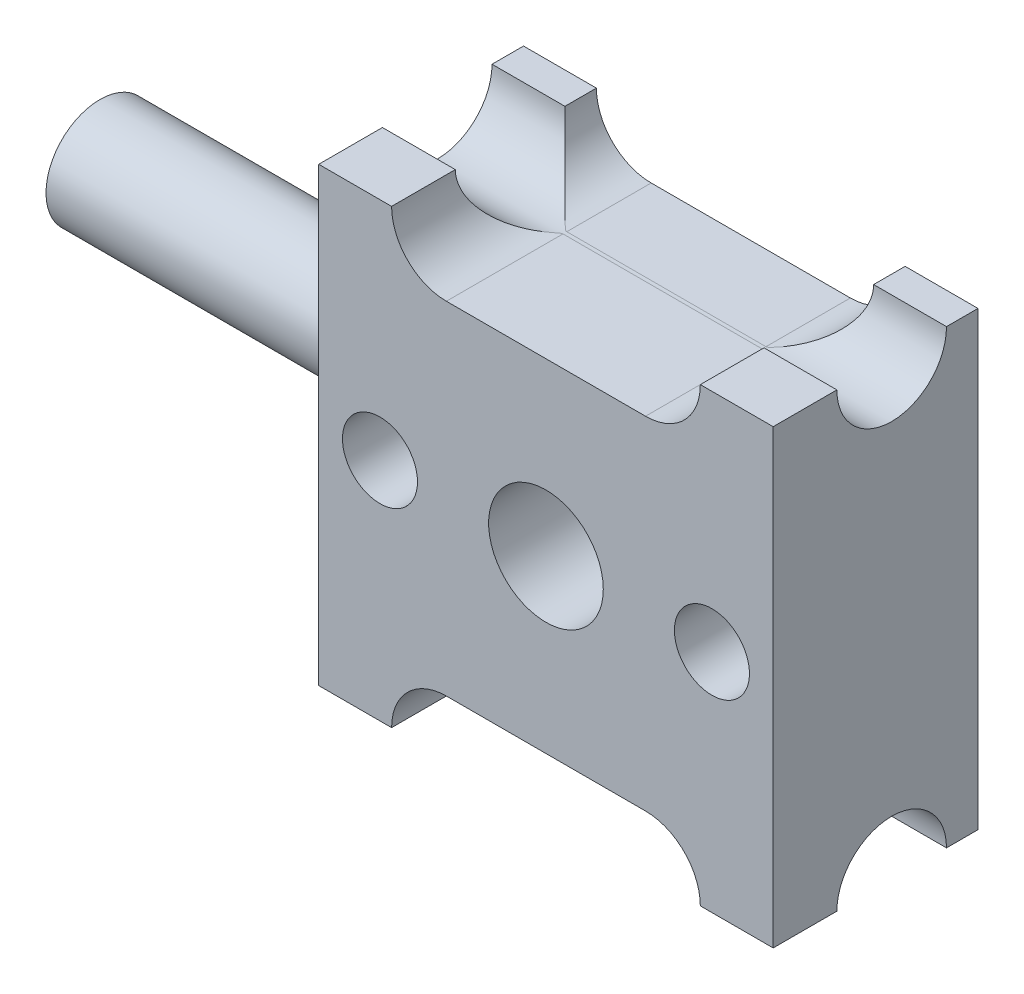
SolidWorks part; units mm, degrees
ref_plane "Front Plane" through (0, 0, 0) normal (0, 0, 1) x (1, 0, 0)
ref_plane "Top Plane" through (0, 0, 0) normal (0, 1, 0) x (1, 0, 0)
ref_plane "Right Plane" through (0, 0, 0) normal (1, 0, 0) x (0, 0, -1)
sketch "Sketch1" plane through (0, 0, 0) normal (0, 0, 1) x (1, 0, 0)
  line L1 (-6.8453, 6.8) -> (6.8453, 6.8)
  line L2 (-6.8453, 6.8) -> (-6.8453, -6.8)
  line L3 (-6.8453, -6.8) -> (6.8453, -6.8)
  line L4 (6.8453, 6.8) -> (6.8453, -6.8)
  line L5 (-6.8453, 6.8) -> (6.8453, -6.8) construction
  line L6 (-6.8453, -6.8) -> (6.8453, 6.8) construction
  point P0 (0, 0)
  dimension "D1" = 13.6906
  dimension "D2" = 13.6
extrude "Boss-Extrude1" add sketch "Sketch1" along normal blind 6.17
sketch "Sketch2" plane through (6.8453, 0, 0) normal (1, 0, 0) x (0, 0, -1)
  line L0 (-6.17, 6.8) -> (0, 6.8) construction
  line L1 (0, -6.8) -> (0, 6.8) construction
  line L2 (-6.17, 0) -> (0, 0) construction
  line L3 (-6.17, -6.8) -> (-6.17, 6.8) construction
  circle A0 centre (-2.6, 6.8) radius 1.651
  circle A1 centre (-2.6, -6.8) radius 1.651
  dimension "D2" = 3.302
  dimension "D1" = 2.6
extrude "Cut-Extrude1" cut sketch "Sketch2" against normal through all
sketch "Sketch3" plane through (0, 0, 6.17) normal (0, 0, 1) x (1, 0, 0)
  line L0 (6.8453, 6.8) -> (-6.8453, 6.8) construction
  line L1 (-3, 6.8) -> (3, 6.8)
  line L2 (-3, 6.8) -> (-3, 5.15)
  line L3 (-3, 5.15) -> (3, 5.15)
  line L4 (3, 6.8) -> (3, 5.15)
  line L5 (0, 5.15) -> (0, 7.1831) construction
  line L6 (-6.8453, 0) -> (0, 5.15) construction
  line L7 (-6.8453, 6.8) -> (-6.8453, -6.8) construction
  line L8 (0, 5.15) -> (6.8453, 0) construction
  line L9 (6.8453, -6.8) -> (6.8453, 6.8) construction
  line L10 (-6.8453, 0) -> (6.8453, 0) construction
  line L11 (0, -5.15) -> (6.8453, 0) construction
  line L12 (-6.8453, 0) -> (0, -5.15) construction
  line L13 (0, -5.15) -> (0, -7.1831) construction
  line L14 (3, -6.8) -> (3, -5.15)
  line L15 (-3, -5.15) -> (3, -5.15)
  line L16 (-3, -6.8) -> (-3, -5.15)
  line L17 (-3, -6.8) -> (3, -6.8)
  line L18 (-4.65, 6.8) -> (4.65, 6.8)
  line L19 (-3, -6.8) -> (3, -6.8)
  arc A0 (3, 5.15) -> (4.65, 6.8) centre (3, 6.8) ccw
  arc A1 (-3, 5.15) -> (-4.65, 6.8) centre (-3, 6.8) cw
  arc A2 (-3, -5.15) -> (-4.65, -6.8) centre (-3, -6.8) ccw
  arc A3 (3, -5.15) -> (4.65, -6.8) centre (3, -6.8) cw
  line M9 (6.8453, 6.8) -> (-6.8453, 6.8)
  line M11 (-6.8453, -6.8) -> (6.8453, -6.8)
  dimension "D2" = 1.65
  dimension "D1" = 1.65
  dimension "D3" = 6
extrude "Cut-Extrude2" cut sketch "Sketch3" against normal through all contours A1 L2 M9 | L4 L2 L3 M9 | L4 A0 M9 | A3 L14 M11 | L16 L14 L15 M11 | L16 A2 M11 region at (0, 5.975, 6.17) region at (-3.7003, 6.0997, 6.17) region at (3.7003, 6.0997, 6.17) region at (0, -5.975, 6.17) region at (3.7003, -6.0997, 6.17) region at (-3.7003, -6.0997, 6.17)
sketch "Sketch4" plane through (0, 0, 6.17) normal (0, 0, 1) x (1, 0, 0)
  circle A0 centre (0, 0) radius 1.7272
  dimension "D1" = 3.4544
extrude "Cut-Extrude3" cut sketch "Sketch4" against normal through all
sketch "Sketch5" plane through (-6.8453, 0, 0) normal (-1, 0, 0) x (0, 0, 1)
  line L0 (2.6, 5.149) -> (2.6, -5.149) construction
  circle A0 centre (2.6, 0) radius 1.6256
  arc A2 (0.949, 6.8) -> (4.251, 6.8) centre (2.6, 6.8) ccw construction
  arc A3 (4.251, -6.8) -> (0.949, -6.8) centre (2.6, -6.8) ccw construction
  dimension "D1" = 3.2512
extrude "Boss-Extrude2" add sketch "Sketch5" along normal blind 10.16
sketch "Sketch6" plane through (0, 0, 6.17) normal (0, 0, 1) x (1, 0, 0)
  line L0 (0, 5.15) -> (0, -5.15) construction
  line L1 (-3, 5.15) -> (3, 5.15) construction
  line L2 (-3, -5.15) -> (3, -5.15) construction
  circle A0 centre (-5, 0) radius 1.1303
  circle A1 centre (5, 0) radius 1.1303
  dimension "D1" = 2.2606
  dimension "D2" = 10
extrude "Cut-Extrude4" cut sketch "Sketch6" against normal through all
